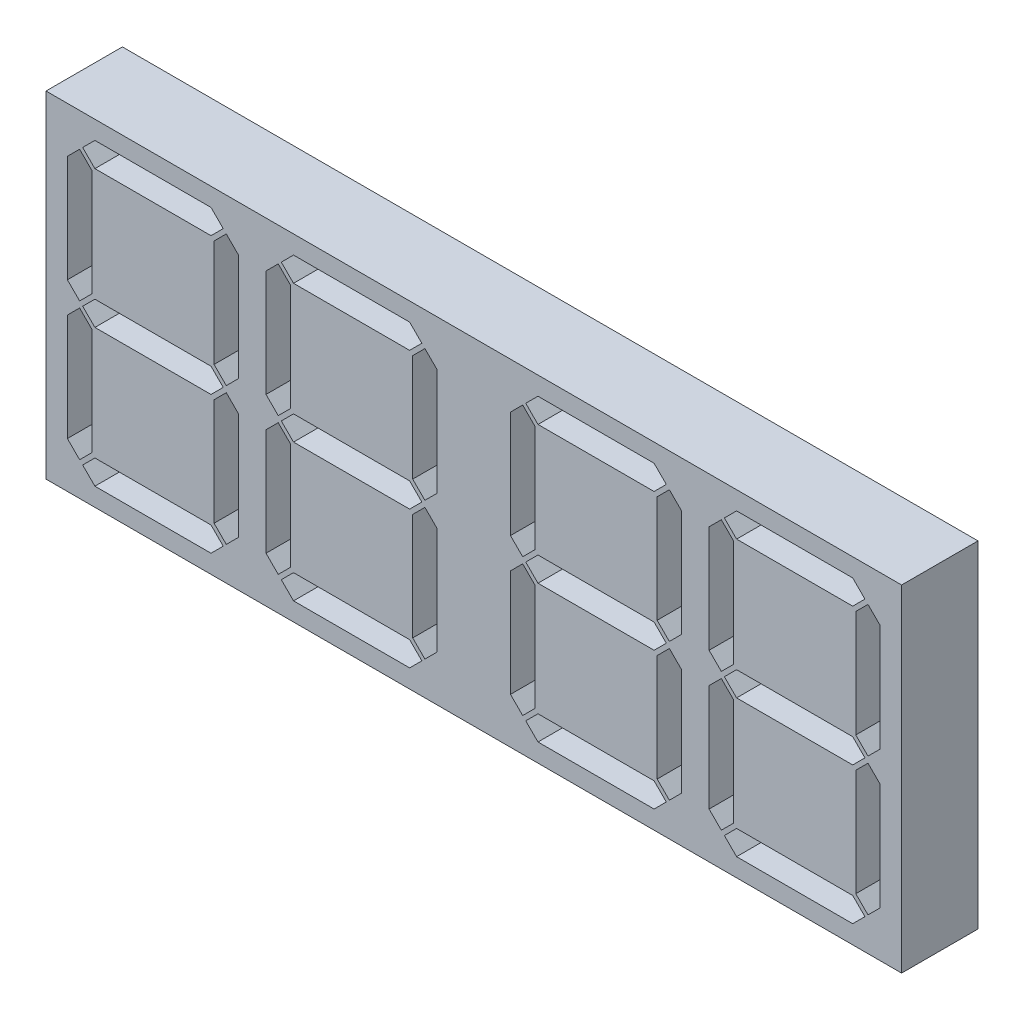
SolidWorks part; units mm, degrees
ref_plane "Front Plane" through (0, 0, 0) normal (0, 0, 1) x (1, 0, 0)
ref_plane "Top Plane" through (0, 0, 0) normal (0, 1, 0) x (1, 0, 0)
ref_plane "Right Plane" through (0, 0, 0) normal (1, 0, 0) x (0, 0, -1)
sketch "Sketch1" plane through (0, 0, 0) normal (0, 0, 1) x (1, 0, 0)
  line L1 (0, 0) -> (140, 0)
  line L2 (0, 0) -> (0, 110)
  line L3 (0, 110) -> (140, 110)
  line L4 (140, 0) -> (140, 110)
  dimension "D1" = 110
  dimension "D2" = 140
extrude "Boss-Extrude1" add sketch "Sketch1" along normal blind 25
sketch "Sketch2" plane through (0, 0, 0) normal (0, 0, -1) x (-1, 0, 0)
  line L0 (-140, 0) -> (-140, 110) construction
  line L1 (-135.2, 4.8) -> (-74.8, 4.8)
  line L2 (-135.2, 4.8) -> (-135.2, 105.2)
  line L3 (-135.2, 105.2) -> (-74.8, 105.2)
  line L4 (-74.8, 4.8) -> (-74.8, 105.2)
  line L5 (-140, 110) -> (0, 110) construction
  line L6 (0, 0) -> (-140, 0) construction
  line L9 (-70.2, 105.2) -> (-9.8, 105.2)
  line L10 (-70.2, 105.2) -> (-70.2, 4.8)
  line L11 (-70.2, 4.8) -> (-9.8, 4.8)
  line L12 (-9.8, 105.2) -> (-9.8, 4.8)
  line L13 (13.75, 0) -> (-13.75, 0) construction
  dimension "D1" = 4.8
  dimension "D2" = 4.8
  dimension "D3" = 4.8
  dimension "D4" = 60.4
  dimension "D5" = 60.4
  dimension "D6" = 4.6
  dimension "D7" = 4.8
  dimension "D8" = 4.8
extrude "Cut-Extrude1" cut sketch "Sketch2" against normal blind 1.6
fillet "Fillet1" radius 3 8 edges at (74.8, 105.2, 0.8) (74.8, 4.8, 0.8) (135.2, 4.8, 0.8) (135.2, 105.2, 0.8) (70.2, 4.8, 0.8) (9.8, 4.8, 0.8) (9.8, 105.2, 0.8) (70.2, 105.2, 0.8)
sketch "Sketch3" plane through (0, 0, 1.6) normal (0, 0, -1) x (-1, 0, 0)
  line L0 (0, 110) -> (0, 0) construction
  line L1 (0, 0) -> (-140, 0) construction
  line L6 (-140, 110) -> (0, 110) construction
  line L7 (-140, 0) -> (-140, 110) construction
  line L8 (13.75, 0) -> (-13.75, 0) construction
  circle A0 centre (-131.5, 101.5) radius 2
  circle A1 centre (-131.5, 8.5) radius 2
  circle A2 centre (-78.5, 8.5) radius 2
  circle A5 centre (-78.5, 101.5) radius 2
  circle A6 centre (-66.5, 101.5) radius 2
  circle A7 centre (-66.5, 8.5) radius 2
  circle A8 centre (-13.5, 8.5) radius 2
  circle A9 centre (-13.5, 101.5) radius 2
  dimension "D3" = 53
  dimension "D17" = 4
  dimension "D18" = 4
  dimension "D19" = 4
  dimension "D20" = 4
  dimension "D21" = 4
  dimension "D22" = 13.5
  dimension "D23" = 8.5
  dimension "D24" = 13.5
  dimension "D4" = 8.5
  dimension "D5" = 8.5
  dimension "D6" = 8.5
  dimension "D7" = 8.5
  dimension "D8" = 8.5
  dimension "D14" = 4
  dimension "D15" = 4
  dimension "D16" = 4
  dimension "D25" = 8.5
  dimension "D26" = 8.5
  dimension "D9" = 93
  dimension "D10" = 53
  dimension "D11" = 53
  dimension "D12" = 93
  dimension "D13" = 53
sketch "Sketch5" plane through (0, 0, 1.6) normal (0, 0, -1) x (-1, 0, 0)
  line L0 (-59, 14) -> (-21, 14)
  line L1 (-124, 14) -> (-86, 14)
  line L2 (-124, 14) -> (-124, 6)
  line L3 (-124, 6) -> (-86, 6)
  line L4 (-86, 14) -> (-86, 6)
  line L5 (-124, 6) -> (-128, 10)
  line L6 (-128, 10) -> (-124, 14)
  line L7 (-86, 14) -> (-82, 10)
  line L8 (-82, 10) -> (-86, 6)
  line L9 (-59, 14) -> (-59, 6)
  line L10 (-86, 59) -> (-86, 51)
  line L11 (-128, 55) -> (-124, 59)
  line L12 (-82, 55) -> (-86, 51)
  line L13 (-124, 59) -> (-86, 59)
  line L14 (-86, 59) -> (-82, 55)
  line L15 (-124, 59) -> (-124, 51)
  line L16 (-124, 51) -> (-86, 51)
  line L17 (-124, 51) -> (-128, 55)
  line L18 (-86, 104) -> (-86, 96)
  line L19 (-128, 100) -> (-124, 104)
  line L20 (-82, 100) -> (-86, 96)
  line L21 (-124, 104) -> (-86, 104)
  line L22 (-86, 104) -> (-82, 100)
  line L23 (-124, 104) -> (-124, 96)
  line L24 (-124, 96) -> (-86, 96)
  line L25 (-124, 96) -> (-128, 100)
  line L26 (-140, 0) -> (-140, 110) construction
  line L27 (-59, 6) -> (-21, 6)
  line L28 (13.75, 0) -> (-13.75, 0) construction
  line L29 (-21, 14) -> (-21, 6)
  line L30 (-59, 6) -> (-63, 10)
  line L31 (-63, 10) -> (-59, 14)
  line L32 (-21, 14) -> (-17, 10)
  line L33 (-17, 10) -> (-21, 6)
  line L34 (-21, 59) -> (-21, 51)
  line L35 (-63, 55) -> (-59, 59)
  line L36 (-17, 55) -> (-21, 51)
  line L37 (-59, 59) -> (-21, 59)
  line L38 (-21, 59) -> (-17, 55)
  line L39 (-59, 59) -> (-59, 51)
  line L40 (-59, 51) -> (-21, 51)
  line L41 (-59, 51) -> (-63, 55)
  line L42 (-21, 104) -> (-21, 96)
  line L43 (-63, 100) -> (-59, 104)
  line L44 (-17, 100) -> (-21, 96)
  line L45 (-59, 104) -> (-21, 104)
  line L46 (-21, 104) -> (-17, 100)
  line L47 (-59, 104) -> (-59, 96)
  line L48 (-59, 96) -> (-21, 96)
  line L49 (-59, 96) -> (-63, 100)
  line L50 (0, 110) -> (0, 0) construction
  dimension "D1" = 38
  dimension "D2" = 8
  dimension "D4" = 4
  dimension "D5" = 4
  dimension "D6" = 46
  dimension "D7" = 4
  dimension "D8" = 12
  dimension "D9" = 38
  dimension "D10" = 8
  dimension "D11" = 4
  dimension "D12" = 4
  dimension "D13" = 46
  dimension "D14" = 4
  dimension "D15" = 38
  dimension "D16" = 8
  dimension "D17" = 4
  dimension "D18" = 4
  dimension "D19" = 46
  dimension "D20" = 4
  dimension "D21" = 12
  dimension "D22" = 12
  dimension "D23" = 6
  dimension "D24" = 38
  dimension "D25" = 8
  dimension "D26" = 4
  dimension "D27" = 4
  dimension "D28" = 46
  dimension "D29" = 4
  dimension "D30" = 38
  dimension "D31" = 8
  dimension "D32" = 4
  dimension "D33" = 4
  dimension "D34" = 46
  dimension "D35" = 4
  dimension "D36" = 38
  dimension "D37" = 8
  dimension "D38" = 4
  dimension "D39" = 37
  dimension "D40" = 4
  dimension "D41" = 37
  dimension "D42" = 46
  dimension "D43" = 4
  dimension "D44" = 37
  dimension "D45" = 37
  dimension "D46" = 17
  dimension "D47" = 17
  dimension "D48" = 17
  dimension "D49" = 6
extrude "Cut-Extrude4" cut sketch "Sketch5" against normal through all contours L23 L24 L18 L21 | L25 L23 L19 | L22 L18 L20 | L15 L16 L10 L13 | L17 L15 L11 | L14 L10 L12 | L4 L1 L2 L3 | L6 L5 L2 | L8 L7 L4 | L46 L42 L44 | L49 L47 L43 | L41 L39 L35 | L39 L40 L34 L37 | L38 L34 L36 | L33 L32 L29 | L29 L0 L9 L27 | L31 L30 L9 | L47 L45 L42 L48 | L36 L38 L34 region at (40, 10, 1.6) region at (60.3333, 10, 1.6) region at (19.6667, 10, 1.6) region at (105, 10, 1.6) region at (125.3333, 10, 1.6) region at (84.6667, 10, 1.6) region at (84.6667, 55, 1.6) region at (105, 55, 1.6) region at (125.3333, 55, 1.6) region at (84.6667, 100, 1.6) region at (105, 100, 1.6) region at (125.3333, 100, 1.6) region at (19.6667, 55, 1.6) region at (40, 55, 1.6) region at (60.3333, 55, 1.6) region at (19.6667, 100, 1.6) region at (60.3333, 100, 1.6)
sketch "Sketch6" plane through (0, 0, 1.6) normal (0, 0, -1) x (-1, 0, 0)
  line L0 (-60, 15) -> (-68, 15)
  line L1 (-125, 15) -> (-133, 15)
  line L2 (-125, 15) -> (-125, 50)
  line L3 (-125, 50) -> (-133, 50)
  line L4 (-133, 15) -> (-133, 50)
  line L5 (-133, 15) -> (-129, 11)
  line L6 (-129, 11) -> (-125, 15)
  line L7 (-133, 50) -> (-129, 54)
  line L8 (-129, 54) -> (-125, 50)
  line L9 (-85, 50) -> (-81, 54)
  line L10 (-77, 15) -> (-85, 15)
  line L11 (-77, 50) -> (-85, 50)
  line L12 (-74.8, 7.8) -> (-74.8, 102.2) construction
  line L13 (-132.2, 4.8) -> (-77.8, 4.8) construction
  line L14 (-85, 15) -> (-81, 11)
  line L15 (-85, 15) -> (-85, 50)
  line L16 (-81, 11) -> (-77, 15)
  line L17 (-81, 54) -> (-77, 50)
  line L18 (-77, 15) -> (-77, 50)
  line L19 (-140, 110) -> (0, 110) construction
  line L22 (-140, 0) -> (-140, 110) construction
  line L24 (0, 0) -> (-140, 0) construction
  line L25 (13.75, 0) -> (-13.75, 0) construction
  line L27 (-60, 15) -> (-60, 50)
  line L30 (-60, 50) -> (-68, 50)
  line L32 (-68, 15) -> (-68, 50)
  line L33 (-68, 15) -> (-64, 11)
  line L35 (-133, 95) -> (-129, 99)
  line L36 (-125, 60) -> (-133, 60)
  line L37 (-125, 95) -> (-133, 95)
  line L38 (-133, 60) -> (-129, 56)
  line L39 (-133, 60) -> (-133, 95)
  line L40 (-129, 56) -> (-125, 60)
  line L41 (-129, 99) -> (-125, 95)
  line L42 (-125, 60) -> (-125, 95)
  line L43 (-85, 95) -> (-81, 99)
  line L44 (-77, 60) -> (-85, 60)
  line L45 (-77, 95) -> (-85, 95)
  line L46 (-85, 60) -> (-81, 56)
  line L47 (-85, 60) -> (-85, 95)
  line L48 (-81, 56) -> (-77, 60)
  line L49 (-81, 99) -> (-77, 95)
  line L50 (-77, 60) -> (-77, 95)
  line L51 (-64, 11) -> (-60, 15)
  line L52 (-68, 50) -> (-64, 54)
  line L53 (-64, 54) -> (-60, 50)
  line L54 (-20, 50) -> (-16, 54)
  line L55 (-12, 15) -> (-20, 15)
  line L56 (-12, 50) -> (-20, 50)
  line L57 (-20, 15) -> (-16, 11)
  line L58 (-20, 15) -> (-20, 50)
  line L59 (-16, 11) -> (-12, 15)
  line L60 (-16, 54) -> (-12, 50)
  line L61 (-12, 15) -> (-12, 50)
  line L62 (-68, 95) -> (-64, 99)
  line L63 (-60, 60) -> (-68, 60)
  line L64 (-60, 95) -> (-68, 95)
  line L65 (-68, 60) -> (-64, 56)
  line L66 (-68, 60) -> (-68, 95)
  line L67 (-64, 56) -> (-60, 60)
  line L68 (-64, 99) -> (-60, 95)
  line L69 (-60, 60) -> (-60, 95)
  line L70 (-20, 95) -> (-16, 99)
  line L71 (-12, 60) -> (-20, 60)
  line L72 (-12, 95) -> (-20, 95)
  line L73 (-20, 60) -> (-16, 56)
  line L74 (-20, 60) -> (-20, 95)
  line L75 (-16, 56) -> (-12, 60)
  line L76 (-16, 99) -> (-12, 95)
  line L77 (-12, 60) -> (-12, 95)
  line L78 (0, 110) -> (0, 0) construction
  dimension "D1" = 35
  dimension "D3" = 8
  dimension "D4" = 11
  dimension "D5" = 4
  dimension "D6" = 4
  dimension "D7" = 4
  dimension "D8" = 4
  dimension "D9" = 11
  dimension "D10" = 8
  dimension "D11" = 11
  dimension "D12" = 4
  dimension "D13" = 4
  dimension "D14" = 4
  dimension "D15" = 4
  dimension "D16" = 4
  dimension "D17" = 7
  dimension "D18" = 7
  dimension "D19" = 11
  dimension "D20" = 4
  dimension "D21" = 35
  dimension "D22" = 35
  dimension "D23" = 35
  dimension "D24" = 8
  dimension "D25" = 4
  dimension "D26" = 4
  dimension "D27" = 35
  dimension "D28" = 8
  dimension "D29" = 4
  dimension "D30" = 4
  dimension "D31" = 4
  dimension "D32" = 4
  dimension "D33" = 4
  dimension "D34" = 8
  dimension "D35" = 4
  dimension "D36" = 4
  dimension "D37" = 4
  dimension "D38" = 8
  dimension "D39" = 4
  dimension "D40" = 4
  dimension "D41" = 35
  dimension "D42" = 8
  dimension "D43" = 4
  dimension "D44" = 4
  dimension "D45" = 4
  dimension "D46" = 4
  dimension "D47" = 8
  dimension "D48" = 4
  dimension "D49" = 4
  dimension "D50" = 40
  dimension "D51" = 40
  dimension "D52" = 40
  dimension "D53" = 4
  dimension "D54" = 4
  dimension "D55" = 4
  dimension "D56" = 4
  dimension "D57" = 35
  dimension "D58" = 40
  dimension "D59" = 35
  dimension "D60" = 11
  dimension "D61" = 11
  dimension "D62" = 12
  dimension "D63" = 12
  dimension "D64" = 11
  dimension "D65" = 11
extrude "Cut-Extrude5" cut sketch "Sketch6" against normal through all contours L36 L42 L37 L39 | L41 L35 L37 | L38 L40 L36 | L8 L7 L3 | L4 L1 L2 L3 | L5 L6 L1 | L10 L18 L11 L15 | L14 L16 L10 | L17 L9 L11 | L46 L48 L44 | L44 L50 L45 L47 | L49 L43 L45 | L63 L69 L64 L66 | L68 L62 L64 | L76 L70 L72 | L71 L77 L72 L74 | L73 L75 L71 | L65 L67 L63 | L53 L52 L30 | L32 L0 L27 L30 | L33 L51 L0 | L57 L59 L55 | L55 L61 L56 L58 | L60 L54 L56 region at (64, 13.6667, 1.6) region at (64, 32.5, 1.6) region at (64, 51.3333, 1.6) region at (129, 13.6667, 1.6) region at (129, 32.5, 1.6) region at (129, 51.3333, 1.6) region at (81, 51.3333, 1.6) region at (81, 32.5, 1.6) region at (81, 13.6667, 1.6) region at (129, 96.3333, 1.6) region at (129, 77.5, 1.6) region at (129, 58.6667, 1.6) region at (81, 96.3333, 1.6) region at (81, 77.5, 1.6) region at (81, 58.6667, 1.6) region at (16, 51.3333, 1.6) region at (16, 32.5, 1.6) region at (16, 13.6667, 1.6) region at (64, 96.3333, 1.6) region at (64, 77.5, 1.6) region at (64, 58.6667, 1.6) region at (16, 96.3333, 1.6) region at (16, 77.5, 1.6) region at (16, 58.6667, 1.6)
sketch "Sketch7" plane through (0, 0, 1.6) normal (0, 0, -1) x (-1, 0, 0)
  line L0 (-125, 95) -> (-124, 96)
  line L1 (-124, 96) -> (-86, 96)
  line L2 (-86, 96) -> (-85, 95)
  line L3 (-85, 95) -> (-85, 60)
  line L4 (-85, 60) -> (-86, 59)
  line L5 (-86, 59) -> (-82, 55) construction
  line L6 (-86, 59) -> (-124, 59)
  line L7 (-124, 59) -> (-125, 60)
  line L8 (-125, 60) -> (-125, 95)
  line L37 (-124, 14) -> (-125, 15)
  line L38 (-125, 15) -> (-125, 50)
  line L39 (-125, 50) -> (-124, 51)
  line L40 (-124, 51) -> (-86, 51)
  line L41 (-86, 51) -> (-85, 50)
  line L42 (-85, 50) -> (-85, 15)
  line L43 (-85, 15) -> (-86, 14)
  line L44 (-86, 14) -> (-124, 14)
  line L61 (-122, 93) -> (-88, 93)
  line L62 (-122, 93) -> (-122, 62)
  line L63 (-122, 62) -> (-88, 62)
  line L64 (-88, 93) -> (-88, 62)
  line L65 (-59, 96) -> (-21, 96) construction
  line L66 (-57, 93) -> (-23, 93)
  line L67 (-57, 93) -> (-57, 62)
  line L68 (-57, 62) -> (-23, 62)
  line L69 (-23, 93) -> (-23, 62)
  line L70 (-57, 48) -> (-23, 48)
  line L71 (-57, 48) -> (-57, 17)
  line L72 (-57, 17) -> (-23, 17)
  line L73 (-23, 48) -> (-23, 17)
  line L74 (-122, 48) -> (-88, 48)
  line L75 (-122, 48) -> (-122, 17)
  line L76 (-122, 17) -> (-88, 17)
  line L77 (-88, 48) -> (-88, 17)
  line L78 (-60, 60) -> (-60, 95) construction
  line L79 (-59, 59) -> (-21, 59) construction
  line L80 (-20, 60) -> (-20, 95) construction
  line L81 (-60, 15) -> (-60, 50) construction
  line L82 (-59, 51) -> (-21, 51) construction
  line L83 (-20, 15) -> (-20, 50) construction
  line L84 (-59, 14) -> (-21, 14) construction
  line L85 (-60, 95) -> (-59, 96)
  line L86 (-59, 96) -> (-21, 96)
  line L87 (-21, 96) -> (-20, 95)
  line L88 (-20, 95) -> (-20, 60)
  line L89 (-20, 60) -> (-21, 59)
  line L90 (-21, 59) -> (-59, 59)
  line L91 (-59, 59) -> (-60, 60)
  line L92 (-60, 60) -> (-60, 95)
  line L93 (-60, 50) -> (-59, 51)
  line L94 (-59, 51) -> (-21, 51)
  line L95 (-21, 51) -> (-20, 50)
  line L96 (-20, 50) -> (-20, 15)
  line L97 (-20, 15) -> (-21, 14)
  line L98 (-21, 14) -> (-59, 14)
  line L99 (-59, 14) -> (-60, 15)
  line L100 (-60, 15) -> (-60, 50)
  line L101 (-12, 50) -> (-11, 51)
  line L102 (-12, 60) -> (-11, 59)
  line L103 (-11, 59) -> (-16, 54)
  line L104 (-11, 51) -> (-16, 56)
  line L105 (-9.8, 7.8) -> (-9.8, 102.2) construction
  line L106 (-11, 59) -> (-9.8, 59)
  line L107 (-11, 59) -> (-11, 51)
  line L108 (-11, 51) -> (-9.8, 51)
  line L109 (-9.8, 59) -> (-9.8, 51)
  line L110 (-16, 54) -> (-12, 50) construction
  line L111 (-16, 56) -> (-12, 60) construction
  line L112 (-77, 50) -> (-76, 51)
  line L113 (-77, 60) -> (-76, 59)
  line L114 (-76, 59) -> (-81, 54)
  line L115 (-76, 51) -> (-81, 56)
  line L116 (-76, 59) -> (-74.8, 59)
  line L117 (-76, 59) -> (-76, 51)
  line L118 (-76, 51) -> (-74.8, 51)
  line L119 (-74.8, 59) -> (-74.8, 51)
  line L120 (-81, 56) -> (-77, 60) construction
  line L121 (-81, 54) -> (-77, 50) construction
  line L122 (-74.8, 7.8) -> (-74.8, 102.2) construction
  line L123 (-68, 60) -> (-69, 59)
  line L124 (-69, 59) -> (-64, 54)
  line L125 (-68, 50) -> (-69, 51)
  line L126 (-69, 51) -> (-64, 56)
  line L127 (-68, 50) -> (-64, 54) construction
  line L128 (-68, 60) -> (-64, 56) construction
  line L129 (-70.2, 102.2) -> (-70.2, 7.8) construction
  line L130 (-69, 51) -> (-70.2, 51)
  line L131 (-69, 51) -> (-69, 59)
  line L132 (-69, 59) -> (-70.2, 59)
  line L133 (-70.2, 51) -> (-70.2, 59)
  line L134 (-133, 60) -> (-134, 59)
  line L135 (-134, 59) -> (-129, 54)
  line L136 (-133, 50) -> (-134, 51)
  line L137 (-134, 51) -> (-129, 56)
  line L138 (-134, 51) -> (-135.2, 51)
  line L139 (-134, 51) -> (-134, 59)
  line L140 (-134, 59) -> (-135.2, 59)
  line L141 (-135.2, 51) -> (-135.2, 59)
  line L142 (-133, 60) -> (-129, 56) construction
  line L143 (-133, 50) -> (-129, 54) construction
  line L144 (-135.2, 102.2) -> (-135.2, 7.8) construction
  point P164 (0, 0)
  point P166 (0, 0)
  point P168 (0, 0)
  point P170 (0, 0)
  line M60 (-85, 60) -> (-85, 95)
  line M65 (-125, 50) -> (-125, 15)
  line M73 (-86, 96) -> (-124, 96)
  line M76 (-74.8, 7.8) -> (-74.8, 102.2)
  line M80 (-135.2, 102.2) -> (-135.2, 7.8)
  line M88 (-124, 14) -> (-86, 14)
  line M90 (-124, 59) -> (-86, 59)
  line M93 (-86, 51) -> (-124, 51)
  line M99 (-125, 95) -> (-125, 60)
  line M102 (-85, 15) -> (-85, 50)
  dimension "D1" = 3
  dimension "D2" = 3
  dimension "D3" = 3
  dimension "D4" = 3
  dimension "D5" = 3
  dimension "D6" = 3
  dimension "D7" = 3
  dimension "D8" = 3
  dimension "D9" = 3
  dimension "D10" = 3
  dimension "D11" = 3
  dimension "D12" = 3
  dimension "D13" = 3
  dimension "D14" = 3
  dimension "D15" = 3
  dimension "D16" = 3
extrude "Cut-Extrude6" cut sketch "Sketch7" against normal blind 1 contours L7 L4 L2 L0 L61 L64 L63 L62 M90 M60 M73 M99 | L43 L41 L39 L37 L74 L77 L76 L75 M102 M93 M65 M88 | L92 L91 L90 L89 L88 L87 L86 L85 L66 L69 L68 L67 | L100 L99 L98 L97 L96 L95 L94 L93 L70 L73 L72 L71 | L107 L103 L104 | L109 L106 L107 L108 | L131 L126 L124 | L133 L130 L131 L132 | L117 L118 L116 M76 | L117 L114 L115 | L139 L137 L135 | L139 L140 L138 M80 region at (124.1147, 95.1147, 1.6) region at (124.1147, 14.8853, 1.6) region at (59.1147, 95.1147, 1.6) region at (59.1147, 50.1147, 1.6) region at (12.3333, 55, 1.6) region at (10.4, 55, 1.6) region at (77.3333, 55, 1.6) region at (75.4, 55, 1.6) region at (67.6667, 55, 1.6) region at (69.6, 55, 1.6) region at (132.6667, 55, 1.6) region at (134.6, 55, 1.6)
extrude "Cut-Extrude7" cut sketch "Sketch3" against normal blind 3.5
mirror "Mirror1" about plane through (0, 0, 25) normal (1, 0, 0) of "Boss-Extrude1", "Fillet1", "Cut-Extrude4", "Cut-Extrude5", "Cut-Extrude6", "Cut-Extrude1", "Cut-Extrude7"
